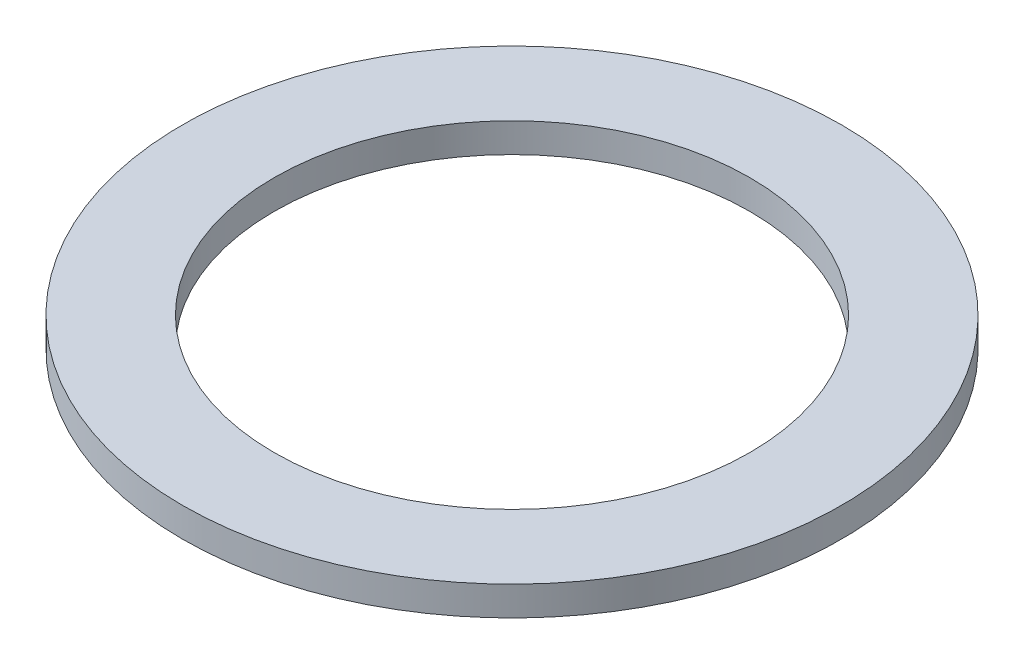
SolidWorks part; units mm, degrees
ref_plane "Front Plane" through (0, 0, 0) normal (0, 0, 1) x (1, 0, 0)
ref_plane "Top Plane" through (0, 0, 0) normal (0, 1, 0) x (1, 0, 0)
ref_plane "Right Plane" through (0, 0, 0) normal (1, 0, 0) x (0, 0, -1)
sketch "Sketch1" plane through (0, 0, 0) normal (0, 1, 0) x (1, 0, 0)
  circle A0 centre (0, 0) radius 45
  dimension "FLANGE_OD" = 90
extrude "Boss-Extrude1" add sketch "Sketch1" along normal blind 4
sketch "Sketch2" plane through (0, 0, 0) normal (0, 1, 0) x (1, 0, 0)
  circle A0 centre (0, 0) radius 32.5
  dimension "BORE_D" = 65
extrude "Cut-Extrude1" cut sketch "Sketch2" along normal through all
sketch "Sketch3" plane through (0, 4, 0) normal (0, 1, 0) x (1, 0, 0)
  circle A0 centre (0, 0) radius 19.2294 construction
  circle A1 centre (-19.2294, 0) radius 2.036
  dimension "BOLT_D" = 4.072
  dimension "BOLT_PCD" = 38.4588
extrude "Cut-Extrude2" cut sketch "Sketch3" against normal blind 3.8676 rebuild error yes
pattern_circular "CirPattern1" count 8 over 360 rebuild error yes
